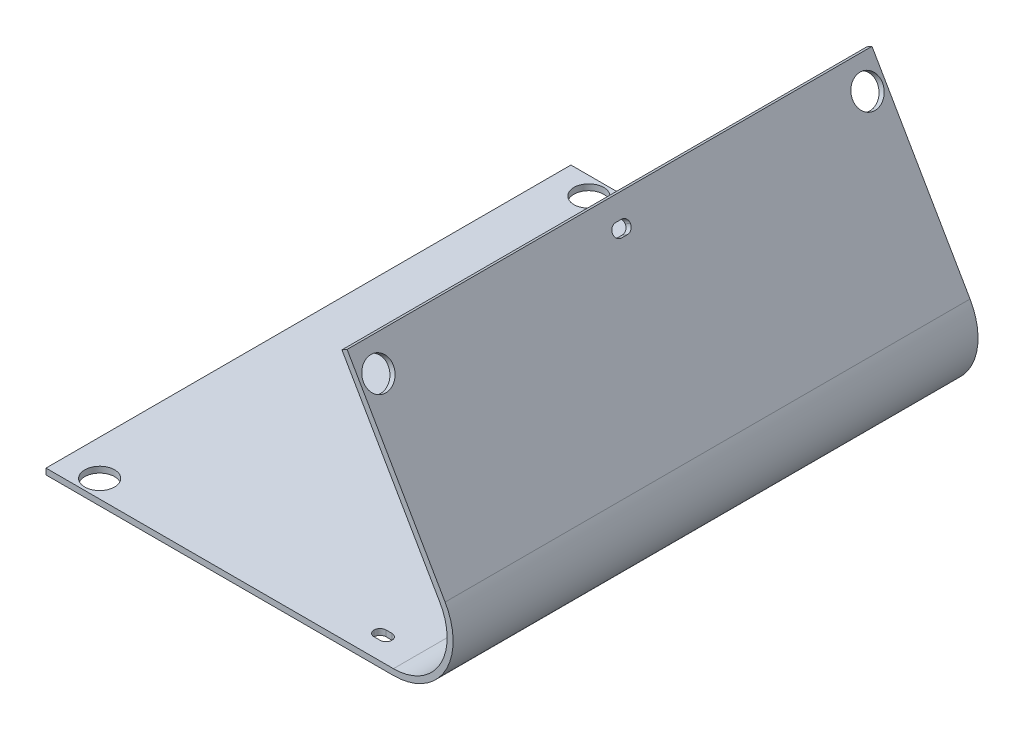
SolidWorks part; units mm, degrees
ref_plane "Płaszczyzna przednia" through (0, 0, 0) normal (0, 0, 1) x (1, 0, 0)
ref_plane "Płaszczyzna górna" through (0, 0, 0) normal (0, 1, 0) x (1, 0, 0)
ref_plane "Płaszczyzna prawa" through (0, 0, 0) normal (1, 0, 0) x (0, 0, -1)
sketch "Szkic1" plane through (0, 0, 0) normal (0, 0, 1) x (1, 0, 0)
  line L0 (-29.125, 0) -> (29.125, 0)
  line L1 (37.7853, 15) -> (21.3503, 43.4663)
  line L2 (-29.125, 1) -> (29.125, 1)
  line L3 (36.9192, 14.5) -> (20.4842, 42.9663)
  line L4 (-29.125, 1) -> (-29.125, 0)
  line L5 (21.3503, 43.4663) -> (20.4842, 42.9663)
  arc A0 (29.125, 0) -> (37.7853, 15) centre (29.125, 10) ccw
  arc A1 (29.125, 1) -> (36.9192, 14.5) centre (29.125, 10) ccw
  dimension "D2" = 10
  dimension "D1" = 60
  dimension "D3" = 58.25
  dimension "D4" = 32.87
extrude "base" add sketch "Szkic1" along normal blind 88
sketch "Szkic3" plane through (0, 1, 0) normal (0, 1, 0) x (1, 0, 0)
  line L0 (-29.125, -88) -> (-29.125, 0) construction
  line L1 (29.125, 0) -> (-29.125, 0) construction
  line L2 (-29.125, -44) -> (83.967, -44) construction
  circle A0 centre (-23.125, -3) radius 2.5
  circle A1 centre (-23.125, -85) radius 2.5
  dimension "D1" = 5
  dimension "D2" = 6
  dimension "D3" = 3
extrude "holes" cut sketch "Szkic3" against normal through all
sketch "Szkic5" plane through (0, 0, 88) normal (0, 0, 1) x (1, 0, 0)
  line L0 (21.3503, 43.4663) -> (21.8503, 42.6002)
  line L1 (21.3503, 43.4663) -> (38.6708, 53.4663)
  line L2 (21.8503, 42.6002) -> (39.1708, 52.6002)
  line L3 (38.6708, 53.4663) -> (39.1708, 52.6002)
  line L4 (37.7853, 15) -> (21.3503, 43.4663) construction
  dimension "D1" = 20
  dimension "D2" = 1
extrude "Dodanie-wyciągnięcie2" [suppressed] add sketch "Szkic5" against normal up to surface (90 mm away)
sketch "Szkic6" plane through (0, 1, 0) normal (0, 1, 0) x (1, 0, 0)
  line L0 (29.125, -88) -> (-29.125, -88) construction
  line L1 (21.875, -83) -> (24.875, -83)
  line L2 (21.875, -83) -> (21.875, -85)
  line L3 (21.875, -85) -> (24.875, -85)
  line L4 (24.875, -83) -> (24.875, -85)
  line L7 (-29.125, -44) -> (104.93, -44) construction
  line L8 (-29.125, -88) -> (-29.125, 0) construction
  line L9 (24.875, -5) -> (24.875, -3)
  line L10 (21.875, -3) -> (24.875, -3)
  line L11 (21.875, -5) -> (21.875, -3)
  line L12 (21.875, -5) -> (24.875, -5)
  dimension "D1" = 3
  dimension "D2" = 2
extrude "Wytnij-wyciągnięcie1" cut sketch "Szkic6" against normal up to next
sketch "Szkic7" plane through (33.9681, 19.6115, 0) normal (-0.866, -0.5, 0) x (0, 0, 1)
  line L7 (44, 26.9678) -> (44, -57.5594) construction
  line L8 (88, 26.9678) -> (0, 26.9678) construction
  circle A0 centre (85, 22.4644) radius 2.5 construction
  circle A1 centre (85, 22.4644) radius 2.5
  circle A2 centre (3, 22.4644) radius 2.5
extrude "Wytnij-wyciągnięcie3" cut sketch "Szkic7" against normal up to next
sketch "Szkic8" plane through (33.9681, 19.6115, 0) normal (-0.866, -0.5, 0) x (0, 0, 1)
  line L0 (88, 26.9678) -> (0, 26.9678) construction
  line L1 (45.5, 21.9678) -> (42.5, 21.9678)
  line L2 (45.5, 21.9678) -> (45.5, 23.9678)
  line L3 (45.5, 23.9678) -> (42.5, 23.9678)
  line L4 (42.5, 21.9678) -> (42.5, 23.9678)
  point P4 (44, 23.9678)
  point P7 (44, 26.9678)
  dimension "D1" = 3
  dimension "D2" = 2
  dimension "D3" = 3
extrude "Wytnij-wyciągnięcie4" cut sketch "Szkic8" against normal up to next
fillet "Zaokrąglenie1" radius 1 12 edges at (22.4172, 40.6182, 42.5) (23.4172, 38.8861, 42.5) (22.4172, 40.6182, 45.5) (23.4172, 38.8861, 45.5) (21.875, 0.5, 85) (24.875, 0.5, 83) (24.875, 0.5, 85) (21.875, 0.5, 83) (21.875, 0.5, 3) (21.875, 0.5, 5) (24.875, 0.5, 3) (24.875, 0.5, 5)
